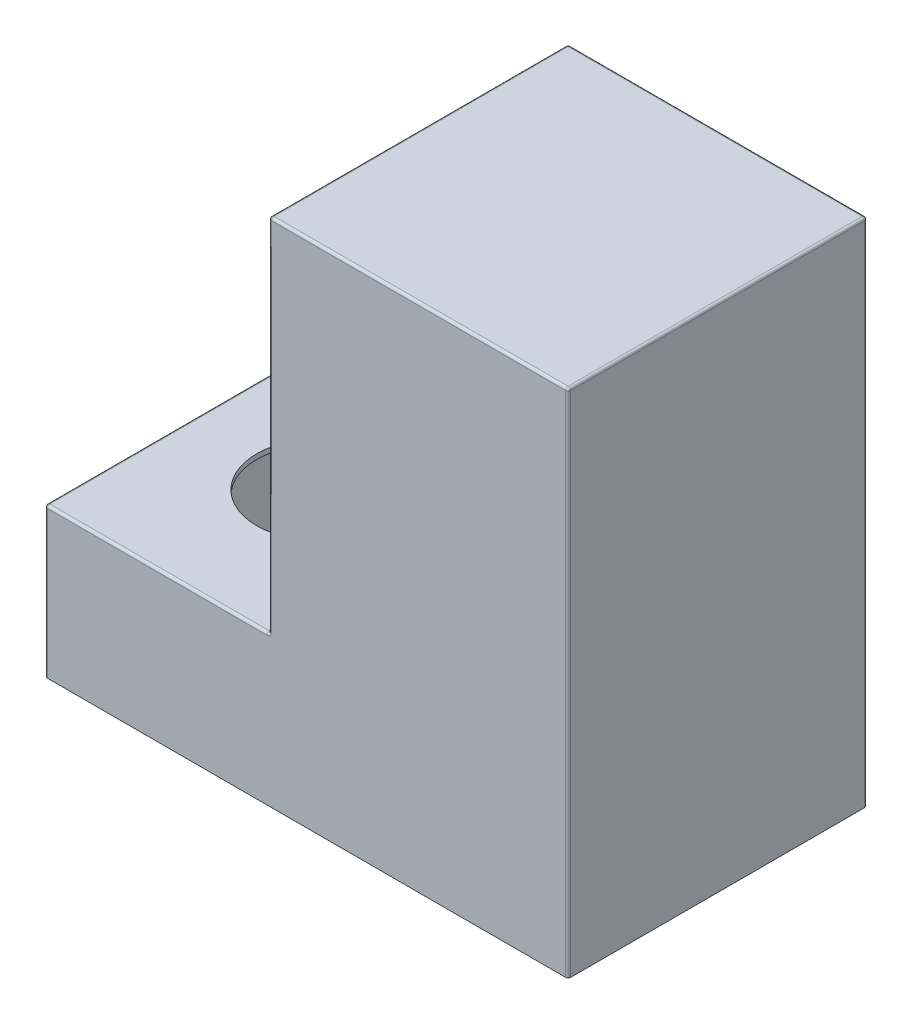
SolidWorks part; units mm, degrees
ref_plane "Front Plane" through (0, 0, 0) normal (0, 0, 1) x (1, 0, 0)
ref_plane "Top Plane" through (0, 0, 0) normal (0, 1, 0) x (1, 0, 0)
ref_plane "Right Plane" through (0, 0, 0) normal (1, 0, 0) x (0, 0, -1)
sketch "Sketch1" plane through (0, 0, 0) normal (0, 0, 1) x (1, 0, 0)
  line L1 (-105, -102.5) -> (105, -102.5)
  line L2 (-105, -102.5) -> (-105, 102.5)
  line L3 (-105, 102.5) -> (105, 102.5)
  line L4 (105, -102.5) -> (105, 102.5)
  line L5 (-105, -102.5) -> (105, 102.5) construction
  line L6 (-105, 102.5) -> (105, -102.5) construction
  point P0 (0, 0)
  dimension "D1" = 210
  dimension "D2" = 205
extrude "Boss-Extrude1" add sketch "Sketch1" along normal blind 120
sketch "Sketch2" plane through (0, 0, 120) normal (0, 0, 1) x (1, 0, 0)
  line L0 (-105, -102.5) -> (105, -102.5) construction
  line L1 (-105, 102.5) -> (-15, 102.5)
  line L2 (-105, 102.5) -> (-105, -42.5)
  line L3 (-105, -42.5) -> (-15, -42.5)
  line L4 (-15, 102.5) -> (-15, -42.5)
  dimension "D1" = 60
  dimension "D2" = 90
extrude "Cut-Extrude1" cut sketch "Sketch2" against normal blind 120
sketch "Sketch3" plane through (0, -102.5, 0) normal (0, -1, 0) x (1, 0, 0)
  line L0 (-105, 0) -> (105, 0) construction
  line L1 (-15, 2) -> (-103, 2)
  line L2 (-15, 2) -> (-15, 118)
  line L3 (-15, 118) -> (-103, 118)
  line L4 (-103, 2) -> (-103, 118)
  line L5 (105, 120) -> (105, 0) construction
  line L6 (-105, 120) -> (105, 120) construction
  dimension "D1" = 2
  dimension "D2" = 120
  dimension "D3" = 2
  dimension "D4" = 88
extrude "Cut-Extrude4" cut sketch "Sketch3" against normal blind 58
sketch "Sketch6" plane through (0, -102.5, 0) normal (0, -1, 0) x (-1, 0, 0)
  line L0 (-105, -120) -> (-105, 0) construction
  line L1 (-103, -2) -> (13, -2)
  line L2 (-103, -2) -> (-103, -118)
  line L3 (-103, -118) -> (13, -118)
  line L4 (13, -2) -> (13, -118)
  line L5 (105, 0) -> (-105, 0) construction
  line L6 (105, -120) -> (-105, -120) construction
  dimension "D1" = 2
  dimension "D2" = 2
  dimension "D3" = 2
  dimension "D4" = 116
extrude "Cut-Extrude6" cut sketch "Sketch6" against normal blind 203
sketch "Sketch7" plane through (0, -102.5, 0) normal (0, -1, 0) x (-1, 0, 0)
  line L1 (13, -2) -> (15, -2)
  line L2 (13, -2) -> (13, -118)
  line L3 (13, -118) -> (15, -118)
  line L4 (15, -2) -> (15, -118)
extrude "Cut-Extrude7" cut sketch "Sketch7" against normal blind 58
fillet "Fillet1" radius 1 11 edges at (105, 0, 120) (45, 102.5, 120) (-15, 102.5, 60) (-105, -72.5, 120) (-60, -42.5, 120) (-15, 30, 120) (-15, 30, 0) (-15, -42.5, 60) (-60, -42.5, 0) (-103, -44.5, 60) (-105, -72.5, 0)
fillet "Fillet2" radius 1 5 edges at (104.7071, 102.2071, 119.7071) (-14.7071, 102.2071, 0.2929) (105, 102.5, 59.5) (45.5, 102.5, 0) (105, 0, 0)
fillet "Fillet3" radius 1 3 edges at (-104.7071, -42.7929, 0.2929) (-104.7071, -42.7929, 119.7071) (-105, -42.5, 60)
sketch "Sketch8" plane through (0, -42.5, 0) normal (0, 1, 0) x (1, 0, 0)
  line L0 (105, -1) -> (105, -119) construction
  line L1 (-104, 0) -> (-16, 0) construction
  circle A0 centre (-55, -60) radius 25
  dimension "D3" = 50
  dimension "D1" = 160
  dimension "D2" = 60
extrude "Cut-Extrude8" cut sketch "Sketch8" against normal blind 58
